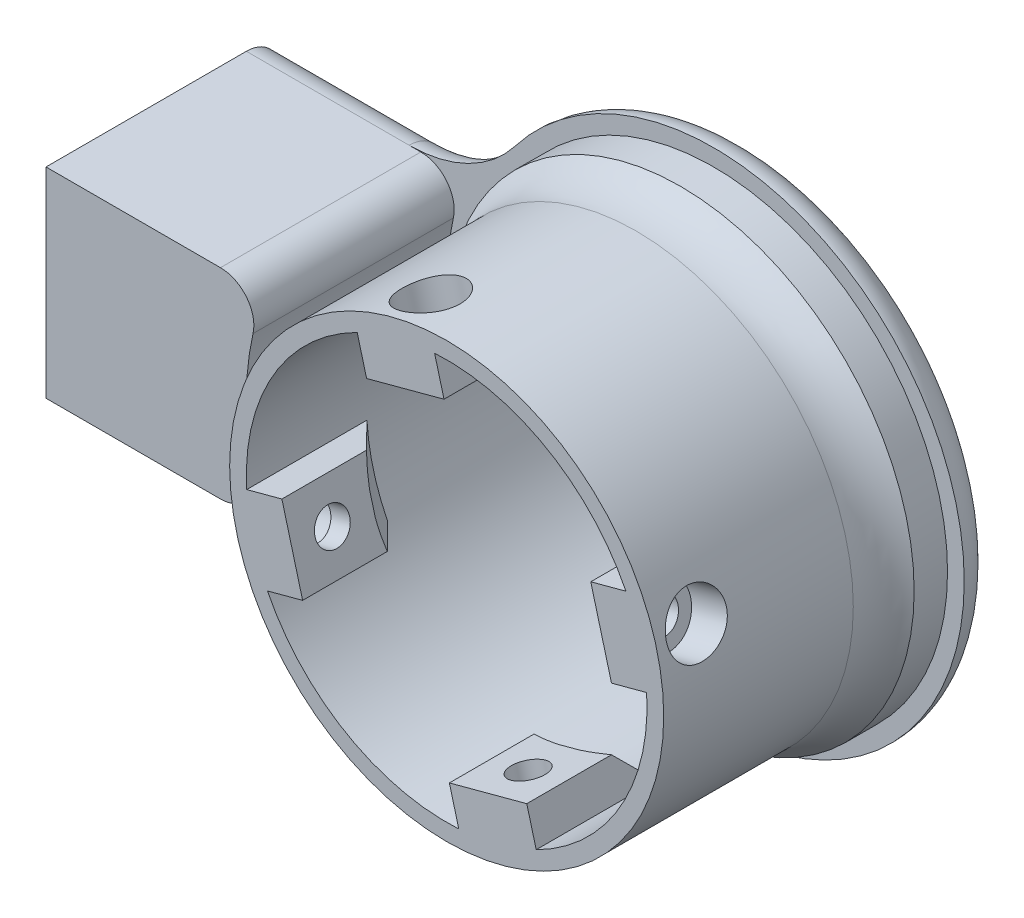
SolidWorks part; units mm, degrees
ref_plane "Plan de face" through (0, 0, 0) normal (0, 0, 1) x (1, 0, 0)
ref_plane "Plan de dessus" through (0, 0, 0) normal (0, 1, 0) x (1, 0, 0)
ref_plane "Plan de droite" through (0, 0, 0) normal (1, 0, 0) x (0, 0, -1)
sketch "Esquisse1" plane through (0, 0, 0) normal (0, 0, 1) x (1, 0, 0)
  line L0 (-1000, 0) -> (49000, 0) construction
  line L1 (-45.6207, 15) -> (-70, 15)
  line L4 (-70, -15) -> (-70, 15)
  line L5 (-45.6207, -15) -> (-70, -15)
  arc A0 (-29.7526, -22.8261) -> (-29.7526, 22.8261) centre (0, 0) ccw
  circle A1 centre (0, 0) radius 30
  arc A2 (-45.6207, 15) -> (-29.7526, 22.8261) centre (-45.6207, 35) ccw
  arc A3 (-45.6207, -15) -> (-29.7526, -22.8261) centre (-45.6207, -35) cw
  point P8 (-34.3693, -15)
  point P9 (-70, 0)
  point P13 (-70, 0)
  point P20 (-34.3693, 15)
  dimension "D1" = 75
  dimension "D4" = 60
  dimension "D5" = 20
  dimension "D2" = 15
  dimension "D3" = 70
extrude "Boss.-Extru.1" add sketch "Esquisse1" along normal blind 5
sketch "Esquisse6" plane through (0, 0, 5) normal (0, 0, 1) x (1, 0, 0)
  circle A0 centre (0, 0) radius 35
  circle A1 centre (0, 0) radius 30
  dimension "D1" = 70
  dimension "D2" = 60
extrude "Boss.-Extru.6" add sketch "Esquisse6" along normal blind 5
sketch "Esquisse7" plane through (0, 0, 10) normal (0, 0, 1) x (1, 0, 0)
  circle A0 centre (0, 0) radius 30
  circle A1 centre (0, 0) radius 32.5
  dimension "D1" = 65
extrude "Boss.-Extru.8" add sketch "Esquisse7" along normal blind 35
fillet "Congé2" radius 10 1 edges at (32.5, 0, 10)
sketch "Esquisse8" plane through (0, 0, 5) normal (0, 0, 1) x (1, 0, 0)
  line L1 (-1000, 0) -> (49000, 0) construction
  line L3 (-70, -15) -> (-70, 15)
  line L9 (-70, -15) -> (-43.8748, -15)
  line L10 (-70, 15) -> (-43.8748, 15)
  line L20 (-70, 15) -> (-70, -15) construction
  arc A2 (-38.9998, 8.8889) -> (-38.9998, -8.8889) centre (0, 0) ccw
  arc A3 (-43.8748, -15) -> (-38.9998, -8.8889) centre (-43.8748, -10) ccw
  arc A4 (-43.8748, 15) -> (-38.9998, 8.8889) centre (-43.8748, 10) cw
  point P4 (-37.081, -15)
  point P5 (-70, 0)
  point P14 (-37.081, 15)
  point P16 (-70, 0)
  dimension "D1" = 80
  dimension "D2" = 5
extrude "Boss.-Extru.9" add sketch "Esquisse8" along normal blind 30
sketch "Esquisse9" plane through (0, 0, 45) normal (0, 0, 1) x (1, 0, 0)
  line L7 (-1000, 0) -> (49000, 0) construction
  line L8 (0, 0) -> (-3034.415, -813.0691) construction
  line L11 (-32.4059, -2.4715) -> (-29.3001, -14.0626)
  line L13 (-32.4059, -2.4715) -> (-24.6785, -0.4009)
  line L15 (-24.6785, -0.4009) -> (-21.5727, -11.992)
  line L17 (-29.3001, -14.0626) -> (-21.5727, -11.992)
  circle A2 centre (0, 0) radius 32.5 construction
  point P22 (0, 0)
  dimension "D1" = 15
  dimension "D2" = 12
  dimension "D5" = 8
extrude "Boss.-Extru.10" add sketch "Esquisse9" against normal blind 12
chamfer "Chanfrein1" distance 6 angle 45 1 edges at (-28.9778, -7.7646, 33)
fillet "Congé3" radius 5 5 edges at (37.5, 0, 0) (-57.8104, 15, 0) (-57.8104, -15, 0) (-36.7742, -17.0629, 0) (-36.7742, 17.0629, 0)
sketch "Esquisse10" plane through (-23.1256, -6.1965, 0) normal (0.9659, 0.2588, 0) x (0, 0, -1)
  line L0 (-45, 32.5) -> (-45, -32.5) construction
  circle A0 centre (-39, 0) radius 4.5
  dimension "D1" = 9
  dimension "D2" = 6
extrude "Enlèv. mat.-Extru.1" cut sketch "Esquisse10" against normal up to next
sketch "Esquisse11" plane through (-23.1256, -6.1965, 0) normal (0.9659, 0.2588, 0) x (0, 0, -1)
  line L0 (-45, 32.5) -> (-45, -32.5) construction
  circle A0 centre (-39, 0) radius 2.6
  circle A1 centre (-39, 0) radius 4.5
  dimension "D2" = 5.2
  dimension "D3" = 9
  dimension "D1" = 6
extrude "Boss.-Extru.11" add sketch "Esquisse11" against normal blind 3
pattern_circular "Répétition circulaire1" count 4 every 90 about axis through (0, 0, 45) along (0, 0, 1) of "Chanfrein1", "Boss.-Extru.10", "Boss.-Extru.11", "Enlèv. mat.-Extru.1"
